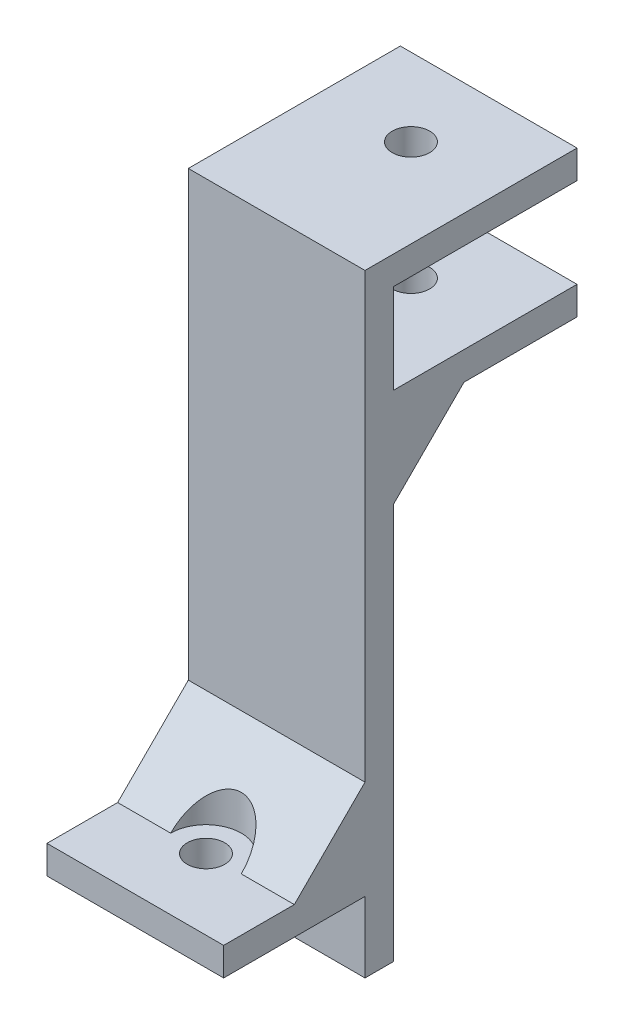
SolidWorks part; units mm, degrees
ref_plane "Front Plane" through (0, 0, 0) normal (0, 0, 1) x (1, 0, 0)
ref_plane "Top Plane" through (0, 0, 0) normal (0, 1, 0) x (1, 0, 0)
ref_plane "Right Plane" through (0, 0, 0) normal (1, 0, 0) x (0, 0, -1)
sketch "Sketch1" plane through (0, 0, 0) normal (1, 0, 0) x (0, 0, -1)
  line L0 (0, 0) -> (0, 10)
  line L1 (4, 70) -> (30, 70)
  line L7 (0, 86.7) -> (30, 86.7)
  line L8 (30, 86.7) -> (30, 82.7)
  line L9 (30, 82.7) -> (4, 82.7)
  line L10 (4, 82.7) -> (4, 70)
  line L11 (0, 14) -> (-20, 14)
  line L12 (-20, 14) -> (-20, 10)
  line L13 (-20, 10) -> (0, 10)
  line L14 (0, 14) -> (0, 86.7)
  line L15 (30, 70) -> (30, 66)
  line L16 (30, 66) -> (4, 66)
  line L17 (4, 66) -> (4, 0)
  line L18 (4, 0) -> (0, 0)
  dimension "D1" = 20
  dimension "D2" = 30
  dimension "D3" = 4
  dimension "D4" = 4
  dimension "D5" = 12.7
  dimension "D6" = 4
  dimension "D7" = 60
  dimension "D8" = 10
  dimension "D9" = 4
  dimension "D10" = 4
extrude "Boss-Extrude1" add sketch "Sketch1" along normal blind 25
sketch "Sketch2" plane through (0, 14, 0) normal (0, 1, 0) x (1, 0, 0)
  line L0 (12.5, 0) -> (12.5, -20) construction
  line L1 (25, 0) -> (0, 0) construction
  line L2 (25, -20) -> (0, -20) construction
  circle A0 centre (12.5, -10) radius 2.65
  dimension "D1" = 5.3
  dimension "D2" = 10
extrude "Cut-Extrude1" cut sketch "Sketch2" against normal blind 6 and the other way blind 6
sketch "Sketch3" plane through (0, 86.7, 0) normal (0, 1, 0) x (1, 0, 0)
  line L0 (12.5, 30) -> (12.5, 0) construction
  line L1 (25, 30) -> (0, 30) construction
  line L2 (25, 0) -> (0, 0) construction
  circle A0 centre (12.5, 19) radius 2.65
  dimension "D1" = 5.3
  dimension "D2" = 19
extrude "Cut-Extrude2" cut sketch "Sketch3" against normal through all
chamfer "Chamfer1" distance 10 angle 45 1 edges at (12.5, 14, 0)
sketch "Sketch4" plane through (0, 14, 0) normal (0, 1, 0) x (1, 0, 0)
  circle A0 centre (12.5, -10) radius 5
  dimension "D1" = 10
extrude "Cut-Extrude4" cut sketch "Sketch4" along normal blind 6
chamfer "Chamfer2" distance 10 angle 45 1 edges at (12.5, 66, -4)
